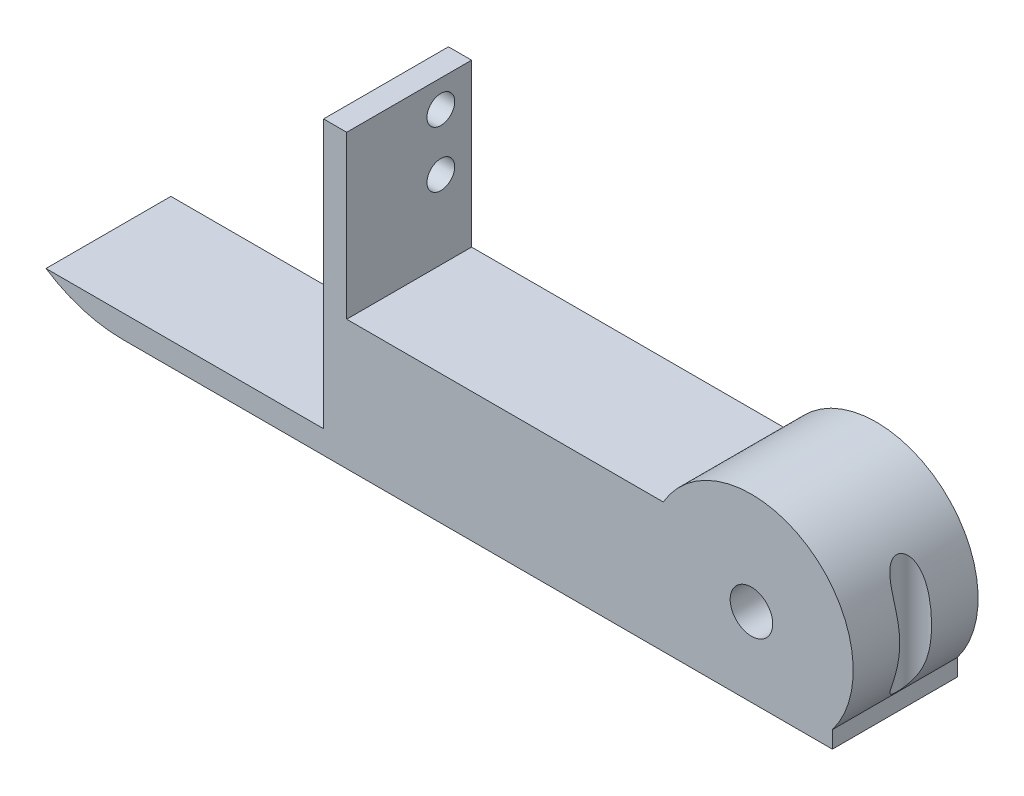
SolidWorks part; units mm, degrees
ref_plane "Plano frontal" through (0, 0, 0) normal (0, 0, 1) x (1, 0, 0)
ref_plane "Plano superior" through (0, 0, 0) normal (0, 1, 0) x (1, 0, 0)
ref_plane "Plano direito" through (0, 0, 0) normal (1, 0, 0) x (0, 0, -1)
sketch "Esboço1" plane through (0, 0, 0) normal (0, 0, 1) x (1, 0, 0)
  line L0 (-85, -14) -> (85, -14)
  line L1 (-85, -14) -> (-85, 14)
  line L2 (-85, 14) -> (48.4474, 14)
  line L3 (85, -10.3323) -> (85, -14)
  line L4 (-85, 14) -> (85, -14) construction
  line L5 (-85, -14) -> (25, 21) construction
  line L6 (67.5, -19) -> (67.5, -14) construction
  arc A1 (85, -10.3323) -> (48.4474, 14) centre (67.5, 3) ccw
  point P2 (0, 0)
  dimension "D3" = 17.5
  dimension "D1" = 28
  dimension "D2" = 170
extrude "Ressalto-extrusão2" add sketch "Esboço1" along normal blind 27
sketch "Esboço2" plane through (0, 0, 27) normal (0, 0, 1) x (1, 0, 0)
  circle A0 centre (67.5, 3) radius 4.6
extrude "Corte-extrusão1" cut sketch "Esboço2" against normal blind 35
sketch "Esboço6" plane through (-85, 0, 0) normal (-1, 0, 0) x (0, 0, 1)
  line L1 (0, 14) -> (27, -14) construction
  line L2 (0, -14) -> (27, 14) construction
  line L3 (13.5, 0) -> (30.4179, -17.9131) construction
  line L4 (30.4179, -17.9131) -> (-3.4654, -17.9131) construction
  line L6 (5, -9) -> (22, -9)
  line L10 (27, 14) -> (0, 14)
  line L12 (27, 14) -> (0, 14) construction
  line L13 (27, -14) -> (0, -14) construction
  line L16 (5, -9) -> (0, -9)
  line L17 (0, 14) -> (0, -14) construction
  line L18 (0, -9) -> (0, 14)
  line L19 (27, 14) -> (27, -9)
  line L20 (27, 14) -> (27, -14) construction
  line L21 (27, -9) -> (22, -9)
  dimension "D3" = 5
extrude "Corte-extrusão3" cut sketch "Esboço6" against normal blind 60
sketch "Esboço7" plane through (-25, 0, 0) normal (-1, 0, 0) x (0, 0, 1)
  line L1 (0, 14) -> (27, 14)
  line L2 (0, 14) -> (0, 49)
  line L3 (0, 49) -> (27, 49)
  line L4 (27, 14) -> (27, 49)
  line L5 (27, -9) -> (27, 14) construction
  dimension "D1" = 35
extrude "Ressalto-extrusão3" add sketch "Esboço7" against normal blind 5
sketch "Esboço8" plane through (-20, 0, 0) normal (1, 0, 0) x (0, 0, -1)
  line L0 (-27, 49) -> (0, 25) construction
  line L1 (0, 25) -> (-27, 25) construction
  line L2 (-27, 25) -> (0, 49) construction
  line L3 (0, 49) -> (-27, 49) construction
  line L4 (-27, 49) -> (-27, 25) construction
  line L5 (-27, 25) -> (0, 25) construction
  line L6 (0, 25) -> (0, 49) construction
  line L7 (-27, 37) -> (0, 37) construction
  line L8 (-13.5, 37) -> (-13.5, 49) construction
  circle A0 centre (-6.6466, 43.0919) radius 3
  circle A2 centre (-6.6466, 30.9081) radius 3
extrude "Corte-extrusão4" cut sketch "Esboço8" against normal through all
sketch "Esboço9" plane through (-25, 0, 0) normal (-1, 0, 0) x (0, 0, 1)
  line L0 (13.5, 49) -> (13.5, -9) construction
  line L1 (27, 49) -> (0, 49) construction
  line L2 (0, -9) -> (27, -9) construction
fillet "Filete1" radius 30 1 edges at (-85, -14, 13.5)
sketch "Esboço12" plane through (0, -14, 0) normal (0, -1, 0) x (1, 0, 0)
  line L0 (85, 27) -> (89.5, 0) construction
  line L1 (89.5, 0) -> (85, 0) construction
  line L2 (85, 0) -> (89.5, 27) construction
  line L3 (89.5, 27) -> (85, 27) construction
  line L4 (87.25, 13.5) -> (89.5, 13.5) construction
  line L5 (89.5, 0) -> (89.5, 27) construction
  circle A0 centre (88.8554, 13.5) radius 3.5
extrude "Corte-extrusão5" cut sketch "Esboço12" against normal through all
